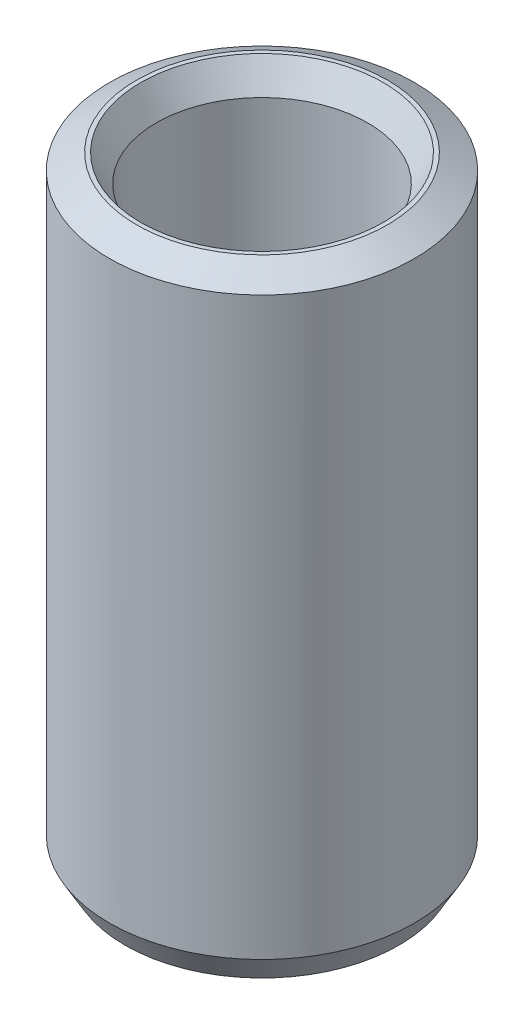
SolidWorks part; units mm, degrees
ref_plane "Front Plane" through (0, 0, 0) normal (0, 0, 1) x (1, 0, 0)
ref_plane "Top Plane" through (0, 0, 0) normal (0, 1, 0) x (1, 0, 0)
ref_plane "Right Plane" through (0, 0, 0) normal (1, 0, 0) x (0, 0, -1)
sketch "Sketch1" plane through (0, 0, 0) normal (0, 1, 0) x (1, 0, 0)
  circle A0 centre (0, 0) radius 30
  dimension "SLEEVE_OD" = 60
extrude "Boss-Extrude1" add sketch "Sketch1" along normal blind 121.595
sketch "Sketch2" plane through (0, 0, 0) normal (0, 1, 0) x (1, 0, 0)
  circle A0 centre (0, 0) radius 20.7757
  dimension "BORE_D" = 41.5514
extrude "Cut-Extrude1" cut sketch "Sketch2" along normal through all
chamfer "Chamfer1" distance 3.0749 angle 60 4 edges at (0, 121.595, 20.7757) (0, 0, 20.7757) (0, 0, 30) (0, 121.595, 30) first distance on face at (0, 121.595, 20.7757) first distance on face at (0, 0, 20.7757) first distance on face at (0, 121.595, 30)
